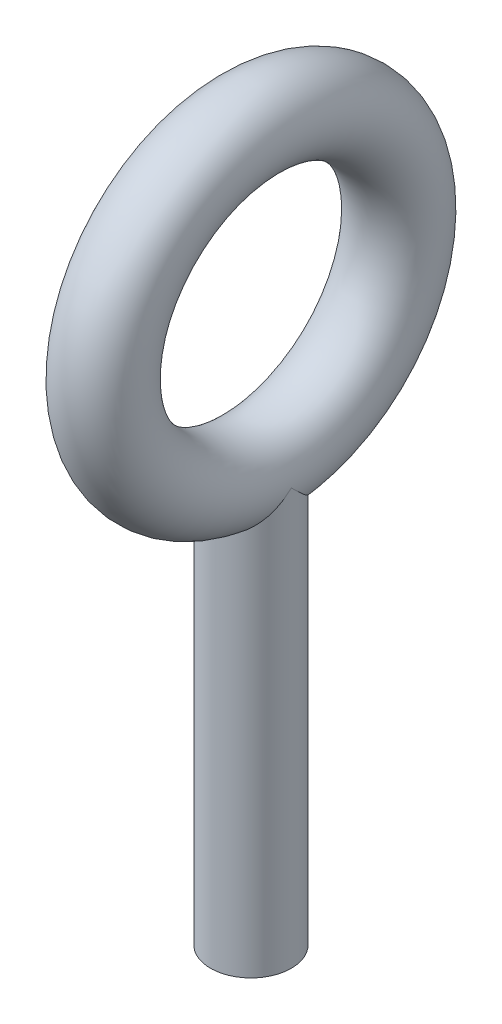
SolidWorks part; units mm, degrees
ref_plane "Front Plane" through (0, 0, 0) normal (0, 0, 1) x (1, 0, 0)
ref_plane "Top Plane" through (0, 0, 0) normal (0, 1, 0) x (1, 0, 0)
ref_plane "Right Plane" through (0, 0, 0) normal (1, 0, 0) x (0, 0, -1)
sketch "Sketch1" plane through (0, 0, 0) normal (0, 0, 1) x (1, 0, 0)
  line L0 (0, 0.5969) -> (0, 3.7719) construction
  line L1 (-0.5969, 0) -> (0.5969, 0)
  line L2 (-0.5969, 0) -> (-0.5969, -6.1468)
  line L3 (-0.5969, -6.1468) -> (0.5969, -6.1468)
  line L4 (0.5969, 0) -> (0.5969, -6.1468)
  line L5 (0, 3.7719) -> (0, 4.9657) construction
  line L6 (0, 0) -> (0, -6.1468)
  circle A0 centre (0, 0) radius 0.5969
  circle A1 centre (0, 4.3688) radius 0.5969 construction
  point P10 (0, 2.1844)
  point P11 (0, 2.1844)
  dimension "D1" = 1.1938
  dimension "D3" = 11.1125
  dimension "D2" = 3.175
sketch "Sketch3" plane through (0, 0, 0) normal (0, 0, 1) x (1, 0, 0)
  line L0 (0, 2.1844) -> (2.6972, 2.1844) construction
revolve "Revolve5" add sketch "Sketch1" angle 360 about L0 region at (0, 0.2533, 0) region at (-0.2533, -0.2533, 0) region at (0.2533, -0.2533, 0)
revolve "Revolve6" add sketch "Sketch1<9>" angle 360 about L6 region at (0.3022, -3.3062, 0)
sketch "Sketch1<9>" plane through (0, 0, 0) normal (0, 0, 1) x (1, 0, 0) same geometry as "Sketch1"
